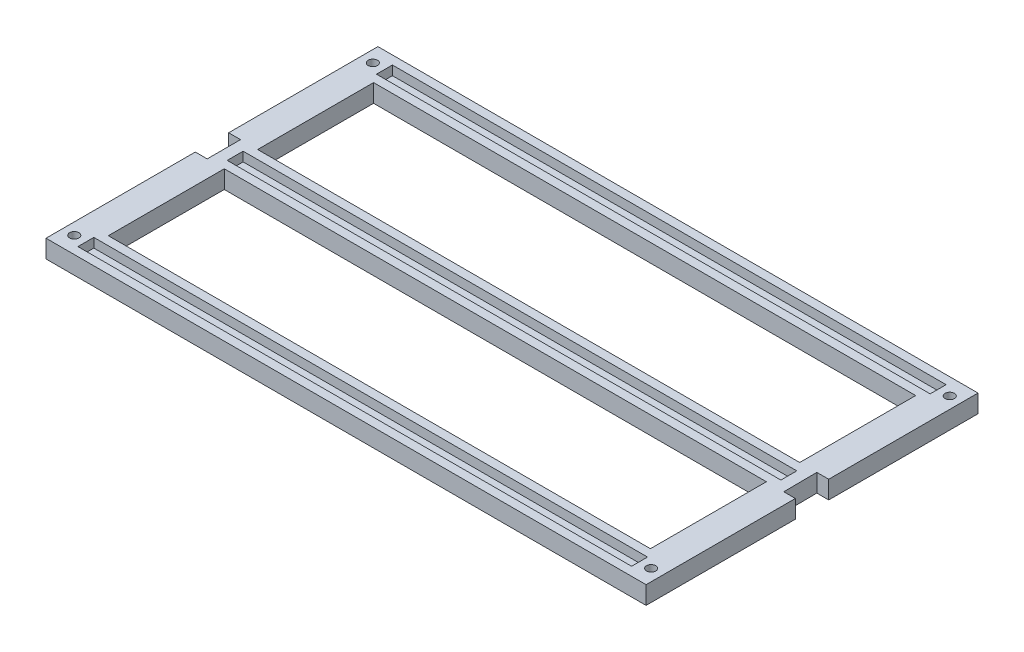
SolidWorks part; units mm, degrees
ref_plane "Front Plane" through (0, 0, 0) normal (0, 0, 1) x (1, 0, 0)
ref_plane "Top Plane" through (0, 0, 0) normal (0, 1, 0) x (1, 0, 0)
ref_plane "Right Plane" through (0, 0, 0) normal (1, 0, 0) x (0, 0, -1)
sketch "Sketch1" plane through (0, 0, 0) normal (0, 1, 0) x (1, 0, 0)
  line L0 (-93.5, 45.75) -> (-93.5, 48.75)
  line L1 (-103.5, -57.25) -> (103.5, -57.25)
  line L2 (-103.5, -57.25) -> (-103.5, 57.25)
  line L3 (-103.5, 57.25) -> (103.5, 57.25)
  line L4 (103.5, -57.25) -> (103.5, 57.25)
  line L5 (0, 57.25) -> (0, -57.25) construction
  line L6 (-103.5, 0) -> (103.5, 0) construction
  line L7 (-93.5, 45.75) -> (93.5, 45.75)
  line L8 (-93.5, 45.75) -> (-93.5, 5.75)
  line L9 (-93.5, 5.75) -> (93.5, 5.75)
  line L10 (93.5, 45.75) -> (93.5, 5.75)
  line L11 (-93.5, -5.75) -> (93.5, -5.75)
  line L12 (-93.5, -5.75) -> (-93.5, -45.75)
  line L13 (-93.5, -45.75) -> (93.5, -45.75)
  line L14 (93.5, -5.75) -> (93.5, -45.75)
  line L15 (-93.5, 48.75) -> (-95.5, 48.75)
  line L16 (-95.5, 48.75) -> (-95.5, 54.25)
  line L17 (-95.5, 54.25) -> (-93.5, 54.25)
  line L18 (-93.5, 54.25) -> (-93.5, 57.25)
  line L19 (93.5, 45.75) -> (93.5, 48.75)
  line L20 (93.5, 48.75) -> (95.5, 48.75)
  line L21 (95.5, 48.75) -> (95.5, 54.25)
  line L22 (95.5, 54.25) -> (93.5, 54.25)
  line L23 (93.5, 54.25) -> (93.5, 57.25)
  line L24 (93.5, 2.75) -> (93.5, 5.75)
  line L25 (95.5, 2.75) -> (93.5, 2.75)
  line L26 (95.5, -2.75) -> (95.5, 2.75)
  line L27 (93.5, -2.75) -> (95.5, -2.75)
  line L28 (93.5, -5.75) -> (93.5, -2.75)
  line L29 (-93.5, 2.75) -> (-93.5, 5.75)
  line L30 (-95.5, 2.75) -> (-93.5, 2.75)
  line L31 (-95.5, -2.75) -> (-95.5, 2.75)
  line L32 (-93.5, -2.75) -> (-95.5, -2.75)
  line L33 (-93.5, -5.75) -> (-93.5, -2.75)
  line L34 (93.5, -48.75) -> (93.5, -45.75)
  line L35 (95.5, -48.75) -> (93.5, -48.75)
  line L36 (95.5, -54.25) -> (95.5, -48.75)
  line L37 (93.5, -54.25) -> (95.5, -54.25)
  line L38 (93.5, -57.25) -> (93.5, -54.25)
  line L39 (-93.5, -48.75) -> (-93.5, -45.75)
  line L40 (-95.5, -48.75) -> (-93.5, -48.75)
  line L41 (-95.5, -54.25) -> (-95.5, -48.75)
  line L42 (-93.5, -54.25) -> (-95.5, -54.25)
  line L43 (-93.5, -57.25) -> (-93.5, -54.25)
  line L44 (-93.5, 54.25) -> (93.5, 54.25)
  line L45 (-93.5, 48.75) -> (93.5, 48.75)
  line L46 (-93.5, 5.75) -> (-103.5, 5.75) construction
  line L47 (93.5, -48.75) -> (-93.5, -48.75)
  line L48 (-93.5, -54.25) -> (93.5, -54.25)
  line L49 (-93.5, 2.75) -> (93.5, 2.75)
  line L50 (95.5, 54.25) -> (103.5, 54.25) construction
  line L51 (95.5, 48.75) -> (103.5, 48.75) construction
  line L52 (99.5, 54.25) -> (99.5, 48.75) construction
  line L53 (0, -55) -> (0, 55) construction
  line L54 (-93.5, -5.75) -> (-103.5, -5.75) construction
  line L55 (93.5, 5.75) -> (103.5, 5.75) construction
  line L56 (93.5, -5.75) -> (103.5, -5.75) construction
  line L57 (-93.5, -2.75) -> (93.5, -2.75)
  line L58 (99.5, -5.75) -> (99.4, 5.75)
  line L59 (99.4, 5.75) -> (103.5, 5.75)
  line L60 (-103.5, 5.75) -> (-99.4, 5.75)
  line L61 (-99.4, 5.75) -> (-99.4, -5.75)
  line L62 (-99.4, -5.75) -> (-103.5, -5.75)
  line L63 (99.5, -5.75) -> (103.5, -5.75)
  circle A0 centre (99.5, 51.5) radius 1.6
  circle A1 centre (-99.5, 51.5) radius 1.6
  circle A2 centre (-99.5, 0) radius 1.6 construction
  circle A3 centre (99.5, 0) radius 1.6 construction
  circle A4 centre (-99.5, -51.5) radius 1.6
  circle A5 centre (99.5, -51.5) radius 1.6
  point P0 (0, 0)
  point P5 (99.5, -5.75)
  dimension "D13" = 3.2
  dimension "D1" = 114.5
  dimension "D2" = 207
  dimension "D3" = 5.5
  dimension "D4" = 11.5
  dimension "D5" = 2
  dimension "D6" = 11.5
  dimension "D7" = 3
  dimension "D8" = 10
  dimension "D9" = 10
  dimension "D10" = 4
  dimension "D11" = 4.1
  dimension "D12" = 3
  dimension "D15" = 4.1
  dimension "D14" = 3
extrude "Boss-Extrude1" add sketch "Sketch1" along normal blind 3.2 contours L18 L44 L23 L3 | L45 L0 L7 L19 | L1 L43 L42 L41 L40 L39 L12 L33 L32 L31 L30 L29 L8 L0 L15 L16 L17 L18 L3 L2 A2 A1 A4 | L29 L24 L9 | L33 L11 L28 | L39 L34 L13 | L43 L1 L38 | L38 L1 L4 L3 L23 L22 L21 L20 L19 L10 L24 L25 L26 L27 L28 L14 L34 L35 L36 L37 A5 A3 A0 region at (-98.4779, 0, 0) region at (0, 0, -47.25) region at (98.4784, 0, 0.0011) region at (0, 0, -4.25) region at (0, 0, -55.75) region at (0, 0, 4.25) region at (0, 0, 47.25) region at (0, 0, 55.75)
extrude "Boss-Extrude2" add sketch "Sketch1<3>" against normal blind 3 contours L38 L1 L4 L3 L23 L22 L21 L20 L19 L10 L24 L25 L26 L27 L28 L14 L34 L35 L36 L37 A5 A3 A0 | L42 L37 L36 L35 L40 L41 | L43 L1 L38 | L39 L34 L13 | L33 L11 L28 | L32 L27 L26 L25 L30 L31 | L29 L24 L9 | L45 L0 L7 L19 | L15 L45 L20 L21 L22 L44 L17 L16 | L18 L44 L23 L3 | L1 L43 L42 L41 L40 L39 L12 L33 L32 L31 L30 L29 L8 L0 L15 L16 L17 L18 L3 L2 A2 A1 A4 region at (-98.4779, 0, 0) region at (0, 0, -47.25) region at (0, 0, -51.5) region at (98.4784, 0, 0.0011) region at (0, 0, -4.25) region at (0, 0, 0) region at (0, 0, -55.75) region at (0, 0, 4.25) region at (0, 0, 47.25) region at (0, 0, 51.5) region at (0, 0, 55.75)
sketch "Sketch1<3>" plane through (0, 0, 0) normal (0, 1, 0) x (1, 0, 0) same geometry as "Sketch1"
